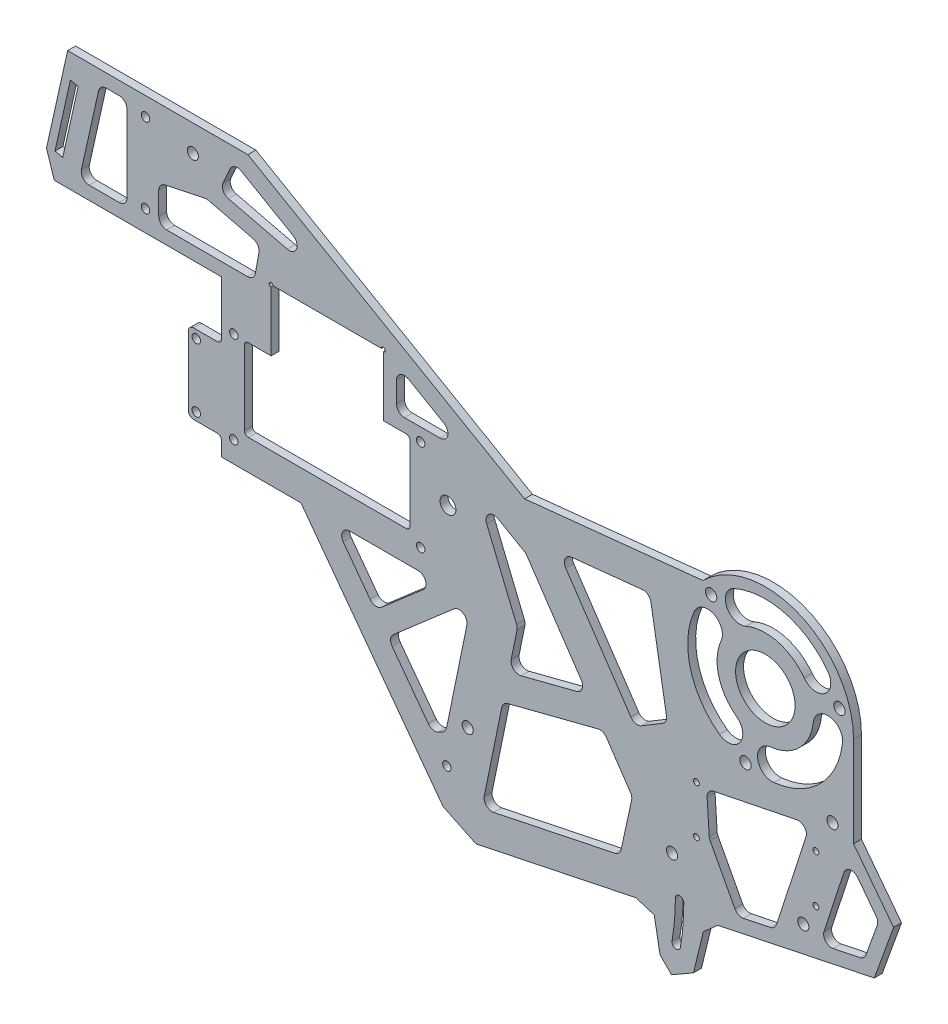
SolidWorks part; units mm, degrees
material "6061 Alloy"
ref_plane "Front Plane" through (0, 0, 0) normal (0, 0, 1) x (1, 0, 0)
ref_plane "Top Plane" through (0, 0, 0) normal (0, 1, 0) x (1, 0, 0)
ref_plane "Right Plane" through (0, 0, 0) normal (1, 0, 0) x (0, 0, -1)
sketch "Sketch1" plane through (0, 0, 0) normal (0, 0, 1) x (1, 0, 0)
  line L1 (20.2869, 47.6) -> (204.7012, 47.6)
  line L2 (20.2869, 47.6) -> (20.2869, -36.0143)
  line L3 (20.2869, -36.0143) -> (204.7012, -36.0143)
  line L4 (204.7012, 47.6) -> (204.7012, -36.0143)
extrude "Boss-Extrude1" add sketch "Sketch1" along normal blind 3
sketch "Sketch2" plane through (0, 0, 0) normal (0, 0, -1) x (-1, 0, 0)
  circle A0 centre (-24.1169, 24) radius 3
  dimension "D1" = 6
extrude "Cut-Extrude1" cut sketch "Sketch2" against normal blind 70
sketch "Sketch3" plane through (0, 0, 3) normal (0, 0, 1) x (1, 0, 0)
  line L0 (24.1169, 24) -> (144.1169, 24) construction
  circle A0 centre (144.1169, 24) radius 11.25
  dimension "D2" = 22.5
  dimension "D1" = 120
extrude "Cut-Extrude2" cut sketch "Sketch3" against normal blind 3
sketch "Sketch4" plane through (0, 0, 3) normal (0, 0, 1) x (1, 0, 0)
  line L0 (-61.5431, 47.6) -> (-61.5431, -3) construction
  line L1 (-61.5431, 56) -> (-61.5431, 34)
  line L2 (-61.5431, 4) -> (-61.5431, -26)
  line L3 (-61.5431, 34) -> (-72.0431, 34)
  line L5 (-61.5431, 4) -> (-72.0431, 4)
  line L6 (-74.0431, 32) -> (-74.0431, 6)
  line L7 (-51.5431, 101) -> (-121.5431, 101)
  line L8 (-121.5431, 101) -> (-121.5431, 56)
  line L9 (-121.5431, 56) -> (-61.5431, 56)
  line L10 (-51.5431, 101) -> (40.9484, 47.6)
  line L11 (20.2869, 47.6) -> (20.2869, -36.0143)
  line L12 (20.2869, -36.0143) -> (204.7012, -36.0143)
  line L13 (204.7012, -36.0143) -> (204.7012, 47.6)
  line L14 (204.7012, 47.6) -> (20.2869, 47.6)
  line L15 (20.2869, 47.6) -> (20.2869, -36.0143)
  line L16 (20.2869, -36.0143) -> (204.7012, -36.0143)
  line L18 (40.9484, 47.6) -> (20.2869, 47.6)
  line L19 (-61.5431, -26) -> (34.7012, -81.5667)
  line L20 (34.7012, -81.5667) -> (204.7012, -81.5667)
  line L21 (204.7012, -81.5667) -> (204.7012, -36.0143)
  line L22 (-85.0431, 56) -> (-64.7431, 56) construction
  circle A0 centre (-71.0431, 31) radius 1.6
  circle A1 centre (-71.0431, 7) radius 1.6
  arc A2 (-72.0431, 4) -> (-74.0431, 6) centre (-72.0431, 6) cw
  arc A3 (-72.0431, 34) -> (-74.0431, 32) centre (-72.0431, 32) ccw
  dimension "D1" = 3.2
  dimension "D2" = 3
  dimension "D5" = 2
  dimension "D3" = 3
  dimension "D4" = 3
  dimension "D7" = 60
  dimension "D8" = 45
  dimension "D9" = 30
  dimension "D10" = 30
  dimension "D11" = 70
  dimension "D12" = 170
  dimension "D6" = 0
extrude "Boss-Extrude2" add sketch "Sketch4" against normal blind 3
sketch "Sketch5" plane through (0, 0, 3) normal (0, 0, 1) x (1, 0, 0)
  line L0 (-0.5431, 62.6) -> (-42.5431, 62.6) construction
  line L1 (8.2869, 8.5) -> (-51.3731, 8.5)
  line L2 (9.7869, 10) -> (9.7869, 38)
  line L3 (8.2869, 39.5) -> (-0.3431, 39.5)
  line L4 (-52.8731, 10) -> (-52.8731, 38)
  line L5 (-41.9931, 62.8) -> (-1.0931, 62.8)
  line L6 (-42.7431, 62.05) -> (-42.7431, 39.5)
  line L8 (-0.3431, 62.05) -> (-0.3431, 39.5)
  line L9 (-42.5431, 57.6) -> (-42.5431, 52.6) construction
  line L10 (-0.5431, 62.6) -> (-0.5431, 57.6) construction
  line L11 (-42.7431, 39.5) -> (-51.3731, 39.5)
  line L13 (7.7869, 47.6) -> (7.7869, -3) construction
  line L14 (-50.8731, -3) -> (-50.8731, 47.6) construction
  line L15 (8.4569, 34.5) -> (-51.5431, 34.5) construction
  line L16 (-51.5431, 13.5) -> (8.4569, 13.5) construction
  arc A0 (9.7869, 38) -> (8.2869, 39.5) centre (8.2869, 38) ccw
  arc A1 (8.2869, 8.5) -> (9.7869, 10) centre (8.2869, 10) ccw
  arc A2 (-51.3731, 8.5) -> (-52.8731, 10) centre (-51.3731, 10) cw
  arc A3 (-51.3731, 39.5) -> (-52.8731, 38) centre (-51.3731, 38) ccw
  arc A4 (-41.9931, 62.8) -> (-42.7431, 62.05) centre (-42.7431, 62.8) ccw
  arc A6 (-1.0931, 62.8) -> (-0.3431, 62.05) centre (-0.3431, 62.8) cw
  dimension "D8" = 1.5
  dimension "D9" = 1.5
  dimension "D10" = 0.75
  dimension "D1" = 0.2
  dimension "D2" = 0.2
  dimension "D3" = 0.2
  dimension "D4" = 2
  dimension "D5" = 2
  dimension "D6" = 5
  dimension "D7" = 5
extrude "Cut-Extrude3" cut sketch "Sketch5" against normal blind 10 contours L8 L5 L6 L3 | L4 L1 L2 L3 region at (-21.5431, 33.186, 3)
sketch "Sketch6" plane through (0, 0, 3) normal (0, 0, 1) x (1, 0, 0)
  line L0 (-61.5431, -3) -> (-50.8731, -3) construction
  line L1 (13.7869, 5) -> (-56.8731, 5) construction
  line L2 (13.7869, 5) -> (13.7869, 39.6) construction
  line L3 (13.7869, 39.6) -> (-56.8731, 39.6) construction
  line L4 (-56.8731, 5) -> (-56.8731, 39.6) construction
  line L5 (-61.5431, 47.6) -> (-50.8731, 47.6) construction
  line L6 (-52.8731, 10) -> (-52.8731, 38) construction
  line L7 (9.7869, 10) -> (9.7869, 38) construction
  circle A0 centre (13.7869, 5) radius 1.6
  circle A1 centre (13.7869, 39.6) radius 1.6
  circle A2 centre (-56.8731, 5) radius 1.6
  circle A3 centre (-56.8731, 39.6) radius 1.6
  dimension "D5" = 3.2
  dimension "D1" = 8
  dimension "D2" = 8
  dimension "D3" = 4
  dimension "D4" = 4
extrude "Cut-Extrude4" cut sketch "Sketch6" against normal blind 3
fillet "Fillet1" radius 1.5 2 edges at (-61.5431, 4, 1.5) (-61.5431, 34, 1.5)
sketch "Sketch8" plane through (0, 0, 3) normal (0, 0, 1) x (1, 0, 0)
  circle A0 centre (-90.2431, 94) radius 1.6
  circle A1 centre (-90.2431, 64) radius 1.6
  dimension "D1" = 3.2
extrude "Cut-Extrude6" cut sketch "Sketch8" against normal blind 12
sketch "Sketch9" plane through (0, 0, 0) normal (0, 0, -1) x (-1, 0, 0)
  circle A0 centre (-172.1287, 31.5058) radius 2.15
  circle A1 centre (-123.6108, 44.5061) radius 2.15
  circle A2 centre (-136.6111, -4.0118) radius 2.15
  dimension "D1" = 4.3
extrude "Cut-Extrude7" cut sketch "Sketch9" against normal blind 12
sketch "Sketch10" plane through (0, 0, 0) normal (0, 0, -1) x (-1, 0, 0)
  line L0 (-204.7012, 47.6) -> (-40.9484, 47.6) construction
  line L1 (-167.6809, 47.6) -> (-120.5529, 47.6)
  arc A0 (-120.5529, 47.6) -> (-167.6809, 47.6) centre (-144.1169, 24) ccw
  dimension "D1" = 66.7
extrude "Boss-Extrude3" add sketch "Sketch10" against normal blind 3
sketch "Sketch12" plane through (0, 0, 3) normal (0, 0, 1) x (1, 0, 0)
  line L0 (34.7012, -81.5667) -> (204.7012, -81.5667) construction
  circle A0 centre (23.7012, -61.5667) radius 1.6
  arc A1 (111.7012, -61.5667) -> (110.4134, -76.5667) centre (23.7012, -61.5667) cw construction
  arc A2 (110.1012, -61.5667) -> (108.8368, -76.294) centre (23.7012, -61.5667) cw
  arc A3 (113.3012, -61.5667) -> (111.99, -76.8394) centre (23.7012, -61.5667) cw
  arc A4 (113.3012, -61.5667) -> (110.1012, -61.5667) centre (111.7012, -61.5667) ccw
  arc A5 (111.99, -76.8394) -> (108.8368, -76.294) centre (110.4134, -76.5667) cw
  dimension "D1" = 3.2
  dimension "D2" = 1.6
  dimension "D3" = 5
extrude "Cut-Extrude8" cut sketch "Sketch12" against normal blind 10
sketch "Sketch13" plane through (0, 0, 0) normal (0, 0, -1) x (-1, 0, 0)
  circle A0 centre (-163.2569, -19.6667) radius 1.1
  circle A1 centre (-163.2569, -37.6667) radius 1.1
  circle A2 centre (-118.0569, -19.6667) radius 1.1
  circle A3 centre (-118.0569, -37.6667) radius 1.1
  dimension "D1" = 2.2
extrude "Cut-Extrude9" cut sketch "Sketch13" against normal blind 10
sketch "Sketch14" plane through (0, 0, 3) normal (0, 0, 1) x (1, 0, 0)
  line L0 (-78.9115, 93.4551) -> (-78.9115, 81.4862)
  line L1 (-78.9115, 81.4862) -> (-54.4003, 81.4862)
  line L2 (-54.4003, 81.4862) -> (-23.8974, 71.6817)
  line L3 (-23.8974, 71.6817) -> (-52.5178, 93.4551)
  line L4 (-52.5178, 93.4551) -> (-78.9115, 93.4551)
  line L5 (-78.9115, 72.578) -> (-70.6821, 62.8507)
  line L6 (-70.6821, 62.8507) -> (-60.2008, 63.6802)
  line L7 (-60.2008, 63.6802) -> (-54.4003, 58.7304)
  line L8 (-54.4003, 58.7304) -> (-54.4003, 45.3567)
  line L9 (-54.4003, 45.3567) -> (-47.2283, 45.9243)
  line L10 (-47.2283, 45.9243) -> (-47.2283, 69.3356)
  line L11 (-47.2283, 69.3356) -> (-63.8202, 74.1615)
  line L12 (-63.8202, 74.1615) -> (-78.9115, 72.578)
  line L13 (4.6513, 57.6299) -> (6.1633, 43.2207)
  line L14 (6.1633, 43.2207) -> (24.148, 52.0435)
  line L15 (24.148, 52.0435) -> (4.6513, 57.6299)
  line L16 (-45.3699, 1.9614) -> (-38.5507, -11.9389)
  line L17 (-38.5507, -11.9389) -> (-7.827, 0.9897)
  line L18 (-7.827, 0.9897) -> (-45.3699, 1.9614)
  line L19 (25.5976, 0.9897) -> (-23.1889, -25.4945)
  line L20 (-23.1889, -25.4945) -> (15.1557, -49.1549)
  line L21 (15.1557, -49.1549) -> (22.7058, -35.0463)
  line L22 (22.7058, -35.0463) -> (25.5976, 0.9897)
  line L23 (40.0766, 31.4181) -> (50.4041, -2.9024)
  line L24 (50.4041, -2.9024) -> (40.0766, -53.4167)
  line L25 (40.0766, -53.4167) -> (100.5808, -42.9603)
  line L26 (100.5808, -42.9603) -> (93.2786, -7.1794)
  line L27 (93.2786, -7.1794) -> (104.3379, 31.4181)
  line L28 (104.3379, 31.4181) -> (40.0766, 31.4181)
  line L29 (128.8509, 35.2778) -> (117.8298, 30.6401)
  line L30 (117.8298, 30.6401) -> (110.8301, -3.5975)
  line L31 (110.8301, -3.5975) -> (123.3404, -3.5975)
  line L32 (123.3404, -3.5975) -> (126.888, 28.7882)
  line L33 (126.888, 28.7882) -> (129.9965, 31.4181)
  line L34 (129.9965, 31.4181) -> (128.8509, 35.2778)
  line L35 (108.9142, -14.8646) -> (113.6543, -38.091)
  line L36 (113.6543, -38.091) -> (133.5452, -30.7552)
  line L37 (133.5452, -30.7552) -> (123.8212, -12.8427)
  line L38 (123.8212, -12.8427) -> (108.9142, -14.8646)
  line L39 (132.2934, -12.8427) -> (142.2048, -27.2848)
  line L40 (142.2048, -27.2848) -> (145.1405, -21.7989)
  line L41 (145.1405, -21.7989) -> (132.2934, -12.8427)
  line L42 (134.3797, 10.2416) -> (133.5452, 2.6233)
  line L43 (133.5452, 2.6233) -> (157.3171, -7.1794)
  line L44 (157.3171, -7.1794) -> (160.734, -2.2781)
  line L45 (160.734, -2.2781) -> (134.3797, 10.2416)
  line L46 (175.8668, 40.8797) -> (188.507, 15.1137)
  line L47 (188.507, 15.1137) -> (177.3665, -23.7672)
  line L48 (177.3665, -23.7672) -> (157.3171, -46.7471)
  line L49 (157.3171, -46.7471) -> (120.319, -62.316)
  line L50 (120.319, -62.316) -> (116.3677, -89.9345)
  line L51 (116.3677, -89.9345) -> (104.3379, -88.2135)
  line L52 (104.3379, -88.2135) -> (104.3379, -66.6352)
  line L53 (104.3379, -66.6352) -> (10.5955, -82.8358)
sketch "Sketch16" plane through (0, 0, 3) normal (0, 0, 1) x (1, 0, 0)
  line L0 (185.3256, -50.1785) -> (192.6101, -29.967)
  line L1 (192.6101, -29.967) -> (177.4666, -10.1551)
  line L2 (177.4666, -10.1551) -> (177.4669, 23.9998)
  line L3 (185.3256, -50.1785) -> (126.1767, -62.5044)
  line L4 (126.1767, -62.5044) -> (120.6914, -67.2922)
  line L5 (120.6914, -67.2922) -> (116.9293, -82.819)
  line L6 (116.9293, -82.819) -> (107.0809, -86.6499)
  line L7 (107.0809, -86.6499) -> (104.3379, -83.2478)
  line L8 (104.3379, -83.2478) -> (102.1139, -71.1635)
  line L9 (102.1139, -71.1635) -> (95.1728, -68.9652)
  line L10 (95.1728, -68.9652) -> (34.7012, -81.5667)
  line L11 (34.7012, -81.5667) -> (-10.3776, -59.7831)
  line L12 (-10.3776, -59.7831) -> (-61.5431, 0.5)
  line L13 (-61.5431, 2.5) -> (-61.5431, -26) construction
  line L14 (167.6809, 47.6) -> (204.7012, 47.6)
  line L15 (204.7012, 47.6) -> (204.7012, -81.5667)
  line L16 (204.7012, -81.5667) -> (109.0158, -101.5063)
  line L17 (109.0158, -101.5063) -> (-44.9012, -81.5667)
  line L18 (-44.9012, -81.5667) -> (-83.4799, -7.1794)
  line L19 (-83.4799, -7.1794) -> (-61.5431, 0.5)
  line L20 (181.5695, -45.8538) -> (186.9817, -30.837)
  line L21 (186.9817, -30.837) -> (175.5875, -15.9302)
  line L22 (175.5875, -15.9302) -> (164.7077, -49.3676)
  line L23 (164.7077, -49.3676) -> (181.5695, -45.8538)
  line L24 (147.7862, -52.8938) -> (133.6464, -55.8404)
  line L25 (133.6464, -55.8404) -> (122.94, -35.6877)
  line L26 (122.94, -35.6877) -> (121.9284, -19.9448)
  line L27 (121.9284, -19.9448) -> (161.094, -11.9946)
  line L28 (161.094, -11.9946) -> (147.7862, -52.8938)
  line L29 (89.1667, -57.959) -> (93.8268, -36.5614)
  line L30 (93.8268, -36.5614) -> (82.8591, -20.3346)
  line L31 (82.8591, -20.3346) -> (44.8433, -30.1016)
  line L32 (44.8433, -30.1016) -> (36.9222, -68.8461)
  line L33 (36.9222, -68.8461) -> (89.1667, -57.959)
  line L34 (76.9131, -11.5374) -> (47.0712, -19.2044)
  line L35 (47.0712, -19.2044) -> (50.4041, -2.9024)
  line L36 (50.4041, -2.9024) -> (35.3223, 33.6)
  line L37 (35.3223, 33.6) -> (46.4046, 33.6)
  line L38 (46.4046, 33.6) -> (76.9131, -11.5374)
  line L39 (94.8609, -13.0907) -> (107.0873, -5.7113)
  line L40 (107.0873, -5.7113) -> (100.3631, 33.6)
  line L41 (100.3631, 33.6) -> (63.3026, 33.6)
  line L42 (63.3026, 33.6) -> (94.8609, -13.0907)
  line L43 (12.3235, -57.4254) -> (22.136, -41.3202)
  line L44 (22.136, -41.3202) -> (30.031, -2.7036)
  line L45 (30.031, -2.7036) -> (-25.069, -30.1108)
  line L46 (-25.069, -30.1108) -> (-11.7658, -45.7846)
  line L47 (-11.7658, -45.7846) -> (12.3235, -57.4254)
  line L48 (-31.7345, -22.2575) -> (1.7886, -5.5828)
  line L49 (1.7886, -5.5828) -> (-2.1286, 0.5)
  line L50 (-2.1286, 0.5) -> (-41.5431, 0.5)
  line L51 (-41.5431, 0.5) -> (-41.5431, -10.701)
  line L52 (-41.5431, -10.701) -> (-31.7345, -22.2575)
  line L53 (32.3178, 44.5) -> (4.6569, 44.5)
  line L54 (4.6569, 44.5) -> (4.6569, 60.47)
  line L55 (4.6569, 60.47) -> (32.3178, 44.5)
  line L56 (-16.3481, 72.5973) -> (-56.8804, 95.9986)
  line L57 (-56.8804, 95.9986) -> (-62.4567, 83.7818)
  line L58 (-62.4567, 83.7818) -> (-16.3481, 72.5973)
  line L59 (-49.1617, 61) -> (-46.8615, 73.8249)
  line L60 (-46.8615, 73.8249) -> (-67.0805, 78.7295)
  line L61 (-67.0805, 78.7295) -> (-85.2431, 74.8953)
  line L62 (-85.2431, 74.8953) -> (-85.2431, 61)
  line L63 (-85.2431, 61) -> (-49.1617, 61)
  line L65 (110.4134, -76.5667) -> (116.9293, -82.819) construction
  line L66 (110.4134, -76.5667) -> (104.3379, -83.2478) construction
  line L67 (120.6914, -67.2922) -> (102.1139, -71.1635) construction
  line L68 (8.2869, 8.5) -> (-51.3731, 8.5) construction
  line L69 (50.4041, -2.9024) -> (40.0766, -53.4167) construction
  line L70 (104.3379, -88.2135) -> (104.3379, -66.6352) construction
  line L72 (8.2869, 39.5) -> (-0.3431, 39.5) construction
  line L73 (-0.3431, 62.05) -> (-0.3431, 39.5) construction
  line L74 (40.9484, 47.6) -> (-51.5431, 101) construction
  line L75 (-121.5431, 56) -> (-61.5431, 56) construction
  line L76 (120.5529, 47.6) -> (40.9484, 47.6) construction
  circle A0 centre (144.1169, 24) radius 33.35 construction
  arc A1 (177.4669, 23.9998) -> (167.6809, 47.6) centre (144.1169, 24) ccw
  circle A2 centre (106.5214, -50.3836) radius 2.1 construction
  circle A3 centre (164.7077, -10.5397) radius 2.1 construction
  circle A4 centre (30.031, -49.0844) radius 2.1 construction
  circle A5 centre (-75.4287, 89.9176) radius 2.1 construction
  circle A6 centre (163.2569, -37.6667) radius 1.1 construction
  circle A7 centre (118.0569, -37.6667) radius 1.1 construction
  circle A8 centre (-90.2431, 64) radius 1.6 construction
  arc A9 (-41.9931, 62.8) -> (-42.7431, 62.05) centre (-42.7431, 62.8) ccw construction
  dimension "D1" = 4.2
  dimension "D5" = 5
  dimension "D2" = 5
  dimension "D3" = 5
  dimension "D4" = 5
  dimension "D6" = 15
  dimension "D7" = 5
  dimension "D8" = 12
  dimension "D9" = 10
  dimension "D10" = 14
  dimension "D11" = 8
  dimension "D12" = 10
  dimension "D13" = 8
  dimension "D14" = 20
  dimension "D15" = 20
  dimension "D16" = 12
  dimension "D17" = 5
  dimension "D18" = 5
  dimension "D19" = 7
  dimension "D20" = 5
  dimension "D21" = 5
  dimension "D22" = 6
  dimension "D23" = 6
  dimension "D24" = 14
  dimension "D25" = 2
extrude "Cut-Extrude10" cut sketch "Sketch16" against normal blind 10
fillet "Fillet2" radius 3 44 edges at (175.5875, -15.9302, 1.5) (186.9817, -30.837, 1.5) (164.7077, -49.3676, 1.5) (181.5695, -45.8538, 1.5) (121.9284, -19.9448, 1.5) (122.94, -35.6877, 1.5) (133.6464, -55.8404, 1.5) (147.7862, -52.8938, 1.5) (94.8609, -13.0907, 1.5) (63.3026, 33.6, 1.5) (35.3223, 33.6, 1.5) (76.9131, -11.5374, 1.5) (89.1667, -57.959, 1.5) (36.9222, -68.8461, 1.5) (50.4041, -2.9024, 1.5) (47.0712, -19.2044, 1.5) (93.8268, -36.5614, 1.5) (82.8591, -20.3346, 1.5) (107.0873, -5.7113, 1.5) (100.3631, 33.6, 1.5) (161.094, -11.9946, 1.5) (46.4046, 33.6, 1.5) (30.031, -2.7036, 1.5) (-25.069, -30.1108, 1.5) (22.136, -41.3202, 1.5) (12.3235, -57.4254, 1.5) (-11.7658, -45.7846, 1.5) (-41.5431, -10.701, 1.5) (-31.7345, -22.2575, 1.5) (1.7886, -5.5828, 1.5) (-2.1286, 0.5, 1.5) (-41.5431, 0.5, 1.5) (4.6569, 60.47, 1.5) (32.3178, 44.5, 1.5) (4.6569, 44.5, 1.5) (-85.2431, 61, 1.5) (-46.8615, 73.8249, 1.5) (-49.1617, 61, 1.5) (-67.0805, 78.7295, 1.5) (-85.2431, 74.8953, 1.5) (-56.8804, 95.9986, 1.5) (-62.4567, 83.7818, 1.5) (-16.3481, 72.5973, 1.5) (44.8433, -30.1016, 1.5)
sketch "Sketch17" plane through (0, 0, 3) normal (0, 0, 1) x (1, 0, 0)
  line L0 (34.7012, -81.5667) -> (-10.3776, -59.7831)
  line L1 (-10.3776, -59.7831) -> (-17.4388, -51.4637)
  line L2 (-17.4388, -51.4637) -> (-61.5431, 0.5) construction
  line L3 (-11.1945, -46.0607) -> (9.8726, -56.241) construction
  line L4 (-17.4388, -51.4637) -> (34.7012, -81.5667) construction
  line L5 (-17.4388, -51.4637) -> (34.7012, -81.5667)
extrude "Boss-Extrude4" add sketch "Sketch17" against normal blind 3
sketch "Sketch18" plane through (0, 0, 3) normal (0, 0, 1) x (1, 0, 0)
  line L0 (-51.5431, 101) -> (-121.5431, 101) construction
  line L1 (-58.251, 92.9958) -> (-60.9482, 87.0866) construction
  line L2 (13.7398, -55.1008) -> (21.8636, -41.7673) construction
  line L3 (44.4676, -31.9395) -> (37.8357, -64.3779) construction
  line L4 (89.5808, -56.0575) -> (93.5536, -37.8159) construction
  line L5 (123.2431, -36.2582) -> (132.5898, -53.8515) construction
  line L6 (173.8201, -21.362) -> (166.3088, -44.4468) construction
  line L7 (177.4669, 23.9998) -> (177.4666, -10.1551) construction
  line L8 (156.0528, -13.0179) -> (124.4933, -19.4241) construction
  circle A0 centre (31.5838, -45.033) radius 2.1
  circle A1 centre (-72.3529, 91) radius 2.1
  circle A2 centre (108.8401, -47.5134) radius 2.1
  circle A3 centre (158.4664, -45.9257) radius 2.1
  circle A4 centre (144.1169, 24) radius 33.35 construction
  circle A5 centre (169.4666, -7.2338) radius 2.1
  dimension "D1" = 4.2
  dimension "D2" = 10
  dimension "D3" = 12
  dimension "D4" = 10
  dimension "D5" = 10
  dimension "D6" = 17
  dimension "D7" = 18
  dimension "D8" = 7
  dimension "D9" = 19
  dimension "D10" = 8
  dimension "D11" = 3
extrude "Cut-Extrude11" cut sketch "Sketch18" against normal blind 3
sketch "Sketch19" plane through (0, 0, 3) normal (0, 0, 1) x (1, 0, 0)
  circle A0 centre (144.1169, 24) radius 29.35
  circle A1 centre (144.1169, 24) radius 18.25
  arc A2 (132.3018, 50.8668) -> (136.7702, 40.706) centre (134.536, 45.7864) ccw
  arc A3 (167.7824, 41.3598) -> (158.8323, 34.7944) centre (163.3073, 38.0771) cw
  arc A4 (162.258, 22.0094) -> (173.2918, 20.7987) centre (167.7749, 21.4041) cw
  arc A5 (146.1075, 5.8589) -> (147.3182, -5.1749) centre (146.7128, 0.342) ccw
  arc A6 (133.3224, 9.2846) -> (126.757, 0.3344) centre (130.0397, 4.8095) cw
  arc A7 (127.4109, 31.3467) -> (117.25, 35.8151) centre (122.3305, 33.5809) ccw
  arc A8 (177.4669, 23.9998) -> (120.5529, 47.6) centre (144.1169, 24) ccw construction
  circle A9 centre (144.1169, 24) radius 11.25 construction
  circle A10 centre (172.1287, 31.5058) radius 2.15 construction
  circle A11 centre (123.6108, 44.5061) radius 2.15 construction
  circle A12 centre (136.6111, -4.0118) radius 2.15 construction
  dimension "D1" = 4
  dimension "D2" = 7
  dimension "D8" = 11
  dimension "D3" = 11
  dimension "D4" = 11
  dimension "D5" = 11
  dimension "D6" = 11
  dimension "D7" = 11
extrude "Cut-Extrude12" cut sketch "Sketch19" against normal blind 3 contours A3 A0 A2 A1 | A1 A7 A0 A6 | A1 A5 A0 A4 region at (149.627, 44.5641, 3) region at (159.1708, 8.946, 3) region at (123.5528, 18.4899, 3)
sketch "Sketch20" plane through (0, 0, 3) normal (0, 0, 1) x (1, 0, 0)
  line L4 (-121.5431, 101) -> (-113.5431, 101)
  line L5 (-113.5431, 101) -> (-121.5431, 65.0628)
  line L6 (-121.5431, 65.0628) -> (-118.5984, 56)
  line L7 (-118.5984, 56) -> (-121.5431, 56)
  line L8 (-121.5431, 56) -> (-121.5431, 101)
  line L9 (-121.5431, 101) -> (-121.5431, 56) construction
  line L10 (-121.5431, 56) -> (-61.5431, 56) construction
  line L11 (-51.5431, 101) -> (-121.5431, 101) construction
  dimension "D2" = 72
  dimension "D3" = 77.45
  dimension "D4" = 8
extrude "Cut-Extrude13" cut sketch "Sketch20" against normal blind 10 contours L8 L5 L4 | L8 L7 L6 region at (-120.5616, 59.0209, 3) region at (-118.8765, 89.0209, 3)
sketch "Sketch21" plane through (0, 0, 3) normal (0, 0, 1) x (1, 0, 0)
  line L0 (117.2327, -81.5667) -> (116.9665, -82.6658)
  line L1 (116.9665, -82.6658) -> (108.6575, -87.4629)
  line L2 (108.6575, -87.4629) -> (104.3143, -83.1198)
  line L3 (104.3143, -83.1198) -> (104.0285, -81.5667)
  line L4 (104.0285, -81.5667) -> (117.2327, -81.5667)
  line L5 (120.6914, -67.2922) -> (117.2327, -81.5667) construction
  line L6 (104.0285, -81.5667) -> (102.1139, -71.1635) construction
  line L7 (110.4134, -76.5667) -> (116.9665, -82.6658) construction
  line L8 (104.3143, -83.1198) -> (110.4134, -76.5667) construction
  dimension "D1" = 30
  dimension "D2" = 45
extrude "Boss-Extrude5" add sketch "Sketch21" against normal blind 3
sketch "Sketch22" plane through (0, 0, 3) normal (0, 0, 1) x (1, 0, 0)
  line L0 (22.246, -75.5479) -> (-29.7449, -5.3216)
  line L1 (-29.7449, -5.3216) -> (-61.5431, -5.3216)
  line L2 (-61.5431, -5.3216) -> (-61.5431, 0.5)
  line L4 (-61.5431, 2.5) -> (-61.5431, 0.5) construction
  line L6 (-10.3776, -59.7831) -> (34.7012, -81.5667) construction
  line L7 (22.246, -75.5479) -> (-101.253, -52.9562)
  line L8 (-101.253, -52.9562) -> (-61.5431, 0.5)
extrude "Cut-Extrude14" cut sketch "Sketch22" against normal blind 10
sketch "Sketch23" plane through (0, 0, 3) normal (0, 0, 1) x (1, 0, 0)
  line L0 (22.246, -75.5479) -> (-31.4636, -3)
  line L1 (-31.4636, -3) -> (-61.5431, -3)
  line L3 (-15.0734, -25.139) -> (-21.1166, -16.9761) construction
  line L4 (22.246, -75.5479) -> (19.933, -56.2587)
  line L5 (19.933, -56.2587) -> (25.986, -38.1223)
  line L6 (25.986, -38.1223) -> (34.1858, 1.8113)
  line L7 (34.1858, 1.8113) -> (9.3649, -1.4066)
  line L8 (9.3649, -1.4066) -> (0.0796, 0.5)
  line L9 (0.0796, 0.5) -> (-61.5431, 0.5)
  line L10 (-61.5431, 0.5) -> (-61.5431, -3)
  line L11 (-74.0431, 32) -> (-74.0431, 6) construction
  line L12 (-51.5431, 101) -> (-113.5431, 101) construction
  dimension "D1" = 42.5795
  dimension "D2" = 74.1227
  dimension "D3" = 83.408
  dimension "D4" = 93.9761
  dimension "D5" = 100.0291
  dimension "D6" = 108.2289
  dimension "D7" = 99.1887
  dimension "D8" = 102.4066
  dimension "D10" = 157.2587
extrude "Boss-Extrude7" add sketch "Sketch23" against normal blind 3
sketch "Sketch24" plane through (0, 0, 3) normal (0, 0, 1) x (1, 0, 0)
  line L0 (-41.5431, -3) -> (-58.5725, -3)
  line L1 (-58.5725, -3) -> (-58.5725, -18.775)
  line L2 (-58.5725, -18.775) -> (-41.5431, -18.775)
  line L3 (-41.5431, -18.775) -> (-41.5431, -3)
extrude "Cut-Extrude15" cut sketch "Sketch24" against normal blind 3
sketch "Sketch25" plane through (0, 0, 3) normal (0, 0, 1) x (1, 0, 0)
  line L0 (16.6752, -51.2169) -> (2.9955, -32.7392)
  line L1 (3.44, -28.6886) -> (26.3557, -8.796)
  line L2 (31.2615, -11.6624) -> (23.5944, -49.1642)
  line L3 (22.1083, -51.1879) -> (20.5394, -52.0565)
  line L4 (-0.9821, -21.9336) -> (14.7631, -8.2655)
  line L5 (12.7965, -3) -> (-13.0677, -3)
  line L6 (-15.4789, -7.785) -> (-5.3599, -21.4532)
  line L7 (44.4676, -31.9395) -> (37.8357, -64.3779) construction
  line L8 (8.2869, 8.5) -> (-51.3731, 8.5) construction
  line L9 (22.246, -75.5479) -> (-31.4636, -3) construction
  line L10 (-61.5431, -3) -> (-31.4636, -3) construction
  line L11 (-74.0431, 32) -> (-74.0431, 6) construction
  circle A0 centre (31.5838, -45.033) radius 2.1 construction
  arc A1 (-13.0677, -3) -> (-15.4789, -7.785) centre (-13.0677, -6) ccw
  arc A2 (-0.9821, -21.9336) -> (-5.3599, -21.4532) centre (-2.9488, -19.6681) cw
  arc A3 (14.7631, -8.2655) -> (12.7965, -3) centre (12.7965, -6) ccw
  arc A4 (2.9955, -32.7392) -> (3.44, -28.6886) centre (5.4066, -30.9541) cw
  arc A5 (26.3557, -8.796) -> (31.2615, -11.6624) centre (28.3223, -11.0615) cw
  arc A6 (16.6752, -51.2169) -> (20.5394, -52.0565) centre (19.0863, -49.4318) ccw
  arc A7 (23.5944, -49.1642) -> (22.1083, -51.1879) centre (20.6552, -48.5633) cw
  point P23 (-19.0214, -3)
  point P26 (-3.4306, -24.0591)
  point P31 (1.3439, -30.5082)
  point P34 (33.0325, -3)
  point P37 (18.2394, -53.3298)
  point P40 (23.3175, -50.5184)
  dimension "D5" = 3
  dimension "D1" = 10
  dimension "D2" = 7
  dimension "D3" = 8
  dimension "D4" = 70.6125
  dimension "D6" = 92.2825
  dimension "D8" = 97.3607
extrude "Cut-Extrude16" cut sketch "Sketch25" against normal blind 3
sketch "Sketch26" plane through (0, 0, 3) normal (0, 0, 1) x (1, 0, 0)
  line L0 (40.9484, 47.6) -> (53.0727, 40.6)
  line L1 (53.0727, 40.6) -> (120.5529, 47.6)
  line L2 (40.9484, 47.6) -> (120.5529, 47.6)
  line L3 (40.9484, 47.6) -> (-51.5431, 101) construction
  dimension "D1" = 7
extrude "Cut-Extrude17" cut sketch "Sketch26" against normal blind 3
sketch "Sketch27" plane through (0, 0, 3) normal (0, 0, 1) x (1, 0, 0)
  line L0 (101.2505, 28.412) -> (100.8633, 30.6761)
  line L1 (106.7424, -3.6944) -> (100.7898, 31.1058) construction
  line L2 (97.5967, 33.1543) -> (70.8103, 30.3756)
  line L3 (66.4657, 28.92) -> (93.265, -10.7296) construction
  line L4 (53.0727, 40.6) -> (120.5529, 47.6) construction
  line L5 (68.6343, 25.7116) -> (74.246, 17.4091)
  line L6 (43.0041, 29.0926) -> (52.9785, 23.3339)
  line L8 (74.5295, -8.011) -> (47.2968, 32.28) construction
  line L9 (53.0727, 40.6) -> (-51.5431, 101) construction
  line L10 (53.964, 22.4158) -> (60.8301, 12.2574)
  line L11 (38.7314, 25.349) -> (40.8011, 20.3397)
  line L12 (37.0352, 29.4544) -> (50.0538, -2.0546) construction
  line L13 (101.2505, 28.412) -> (110.1024, 37.9468)
  line L14 (110.1024, 37.9468) -> (55.5175, 34.9915)
  line L15 (55.5175, 34.9915) -> (74.246, 17.4091)
  line L16 (60.8301, 12.2574) -> (47.3983, 37.9468)
  line L17 (47.3983, 37.9468) -> (28.8837, 36.0262)
  line L18 (28.8837, 36.0262) -> (40.8011, 20.3397)
  line L19 (-85.2431, 72.4624) -> (-85.2431, 64) construction
  line L20 (-51.5431, 101) -> (-113.5431, 101) construction
  arc A0 (70.8103, 30.3756) -> (68.6343, 25.7116) centre (71.1198, 27.3916) ccw
  arc A1 (100.8633, 30.6761) -> (97.5967, 33.1543) centre (97.9062, 30.1703) ccw
  arc A2 (43.0041, 29.0926) -> (38.7314, 25.349) centre (41.5041, 26.4946) ccw
  arc A3 (52.9785, 23.3339) -> (53.964, 22.4158) centre (51.4785, 20.7358) cw
  point P12 (65.831, 29.8591)
  point P29 (53.577, 22.9883)
  dimension "D2" = 3
  dimension "D4" = 3
  dimension "D1" = 12
  dimension "D3" = 15
extrude "Boss-Extrude8" add sketch "Sketch27" against normal blind 3
sketch "Sketch28" plane through (0, 0, 3) normal (0, 0, 1) x (1, 0, 0)
  line L0 (-118.5984, 56) -> (-124.7453, 56)
  line L1 (-124.7453, 56) -> (-127.69, 65.0628)
  line L2 (-127.69, 65.0628) -> (-119.69, 101)
  line L3 (-119.69, 101) -> (-113.5431, 101)
  line L4 (-113.5431, 101) -> (-121.5431, 65.0628)
  line L5 (-121.5431, 65.0628) -> (-118.5984, 56)
  line L6 (-118.5984, 56) -> (-61.5431, 56) construction
  line L7 (-51.5431, 101) -> (-113.5431, 101) construction
  line L8 (-121.5431, 65.0628) -> (-118.5984, 56) construction
  line L9 (-121.5431, 65.0628) -> (-124.4714, 65.7146)
  line L10 (-121.5431, 65.0628) -> (-115.716, 91.2389)
  line L11 (-124.4714, 65.7146) -> (-118.6444, 91.8908)
  line L12 (-115.716, 91.2389) -> (-118.6444, 91.8908)
  line L13 (-113.5431, 101) -> (-121.5431, 65.0628) construction
  dimension "D1" = 3
  dimension "D2" = 3
  dimension "D3" = 10
extrude "Boss-Extrude9" add sketch "Sketch28" against normal blind 3 contours L12 L4 L3 L2 L1 L0 L5 L9 L11 region at (-121.6719, 56.4717, 3)
sketch "Sketch29" plane through (0, 0, 3) normal (0, 0, 1) x (1, 0, 0)
  line L0 (-97.2431, 61) -> (-115.2762, 61)
  line L1 (-115.2762, 61) -> (-107.4848, 96)
  line L2 (-107.4848, 96) -> (-97.2431, 96)
  line L3 (-97.2431, 96) -> (-97.2431, 61)
  line L4 (-82.2431, 61) -> (-51.6715, 61) construction
  line L5 (-51.5431, 101) -> (-119.69, 101) construction
  line L6 (-115.716, 91.2389) -> (-121.5431, 65.0628) construction
  circle A0 centre (-90.2431, 64) radius 1.6 construction
  dimension "D1" = 5
  dimension "D2" = 7
  dimension "D3" = 7
extrude "Cut-Extrude18" cut sketch "Sketch29" against normal blind 3
fillet "Fillet3" radius 3 4 edges at (-107.4848, 96, 1.5) (-97.2431, 96, 1.5) (-97.2431, 61, 1.5) (-115.2762, 61, 1.5)
